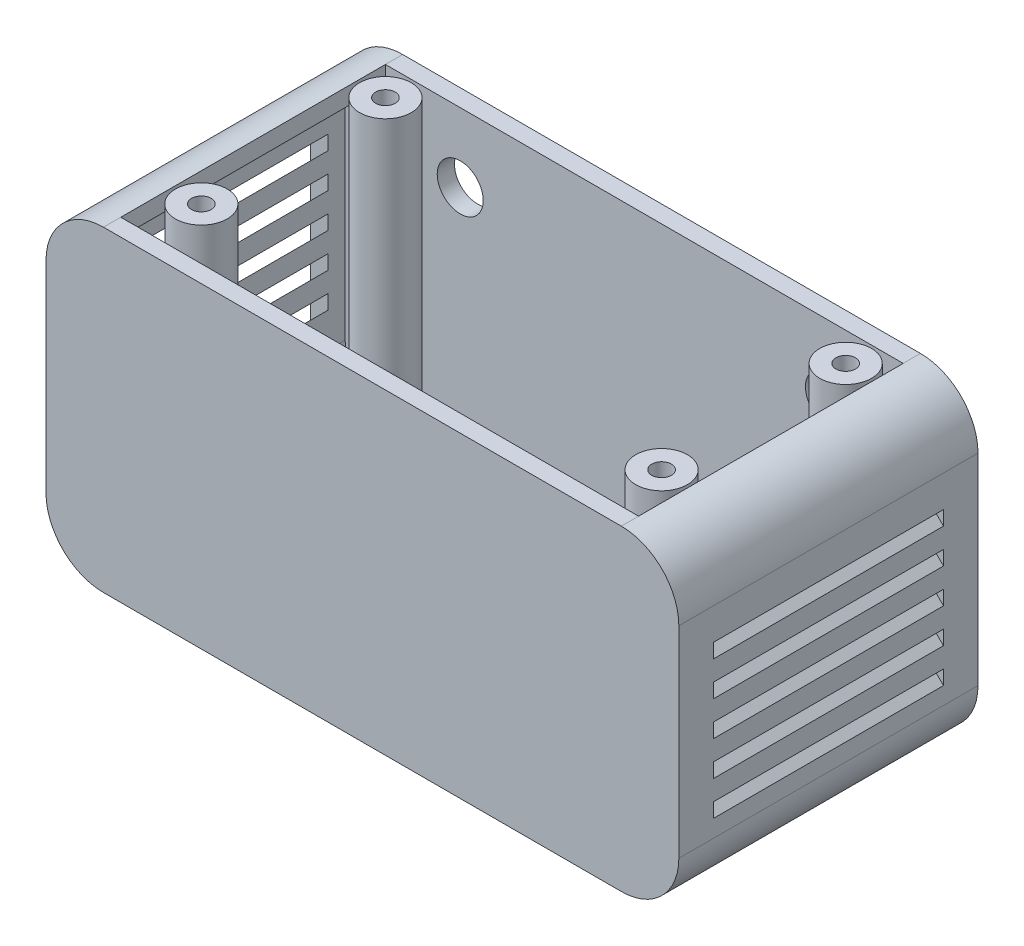
SolidWorks part; units mm, degrees
material "ABS"
ref_plane "Front Plane" through (0, 0, 0) normal (0, 0, 1) x (1, 0, 0)
ref_plane "Top Plane" through (0, 0, 0) normal (0, 1, 0) x (1, 0, 0)
ref_plane "Right Plane" through (0, 0, 0) normal (1, 0, 0) x (0, 0, -1)
sketch "Sketch1" plane through (0, 0, 0) normal (0, 0, 1) x (1, 0, 0)
  line L0 (-45, -55) -> (45, -55)
  line L1 (55, -45) -> (55, -10)
  line L2 (45, 0) -> (-45, 0)
  line L3 (-55, -10) -> (-55, -45)
  arc A0 (45, -55) -> (55, -45) centre (45, -45) ccw
  arc A1 (55, -10) -> (45, 0) centre (45, -10) ccw
  arc A2 (-45, 0) -> (-55, -10) centre (-45, -10) ccw
  arc A3 (-55, -45) -> (-45, -55) centre (-45, -45) ccw
extrude "Boss-Extrude1" add sketch "Sketch1" along normal blind 52
shell "Shell1" thickness 3 removed face at (0, 0, 26)
sketch "Sketch2" plane through (0, 0, 0) normal (0, 1, 0) x (1, 0, 0)
  circle A0 centre (-40, -8) radius 4.5
  circle A1 centre (40, -8) radius 4.5
  circle A2 centre (-40, -40) radius 4.5
  circle A3 centre (40, -40) radius 4.5
extrude "Boss-Extrude2" add sketch "Sketch2" against normal blind 52
sketch "Sketch3" plane through (0, -55, 0) normal (0, -1, 0) x (1, 0, 0)
  circle A0 centre (-40, 8) radius 3.25
  circle A1 centre (40, 8) radius 3.25
  circle A2 centre (-40, 40) radius 3.25
  circle A3 centre (40, 40) radius 3.25
extrude "Cut-Extrude1" cut sketch "Sketch3" against normal blind 49
sketch "Sketch4" plane through (0, -6, 0) normal (0, -1, 0) x (1, 0, 0)
  circle A0 centre (-40, 8) radius 1.7
  circle A1 centre (40, 8) radius 1.7
  circle A2 centre (-40, 40) radius 1.7
  circle A3 centre (40, 40) radius 1.7
extrude "Cut-Extrude2" cut sketch "Sketch4" against normal through all
ref_plane "Plane1" through (0, 0, 26) normal (0, 0, 1) x (1, 0, 0)
sketch "Sketch5" plane through (0, 0, 26) normal (0, 0, 1) x (1, 0, 0)
  line L0 (-51, -14) -> (-51, -11.5)
  line L1 (-51, -11.5) -> (-55.5, -16)
  line L2 (-55.5, -16) -> (-55.5, -18.5)
  line L3 (-55.5, -18.5) -> (-51, -14)
  line L4 (51, -14) -> (51, -11.5)
  line L5 (51, -11.5) -> (55.5, -16)
  line L6 (55.5, -16) -> (55.5, -18.5)
  line L7 (55.5, -18.5) -> (51, -14)
  line L8 (-51, -20) -> (-51, -17.5)
  line L9 (-51, -17.5) -> (-55.5, -22)
  line L10 (-55.5, -22) -> (-55.5, -24.5)
  line L11 (-55.5, -24.5) -> (-51, -20)
  line L12 (51, -20) -> (51, -17.5)
  line L13 (51, -17.5) -> (55.5, -22)
  line L14 (55.5, -22) -> (55.5, -24.5)
  line L15 (55.5, -24.5) -> (51, -20)
  line L16 (-51, -26) -> (-51, -23.5)
  line L17 (-51, -23.5) -> (-55.5, -28)
  line L18 (-55.5, -28) -> (-55.5, -30.5)
  line L19 (-55.5, -30.5) -> (-51, -26)
  line L20 (51, -26) -> (51, -23.5)
  line L21 (51, -23.5) -> (55.5, -28)
  line L22 (55.5, -28) -> (55.5, -30.5)
  line L23 (55.5, -30.5) -> (51, -26)
  line L24 (-51, -32) -> (-51, -29.5)
  line L25 (-51, -29.5) -> (-55.5, -34)
  line L26 (-55.5, -34) -> (-55.5, -36.5)
  line L27 (-55.5, -36.5) -> (-51, -32)
  line L28 (51, -32) -> (51, -29.5)
  line L29 (51, -29.5) -> (55.5, -34)
  line L30 (55.5, -34) -> (55.5, -36.5)
  line L31 (55.5, -36.5) -> (51, -32)
  line L32 (-51, -38) -> (-51, -35.5)
  line L33 (-51, -35.5) -> (-55.5, -40)
  line L34 (-55.5, -40) -> (-55.5, -42.5)
  line L35 (-55.5, -42.5) -> (-51, -38)
  line L36 (51, -38) -> (51, -35.5)
  line L37 (51, -35.5) -> (55.5, -40)
  line L38 (55.5, -40) -> (55.5, -42.5)
  line L39 (55.5, -42.5) -> (51, -38)
extrude "Cut-Extrude3" cut sketch "Sketch5" against normal blind 20 and the other way blind 20
sketch "Sketch6" plane through (0, -55, 0) normal (0, -1, 0) x (1, 0, 0)
  line L0 (-33, 12) -> (-33, 40) construction
  line L1 (-34.5, 12) -> (-34.5, 40)
  line L2 (-31.5, 12) -> (-31.5, 40)
  line L3 (-27, 12) -> (-27, 40) construction
  line L4 (-28.5, 12) -> (-28.5, 40)
  line L5 (-25.5, 12) -> (-25.5, 40)
  line L6 (-21, 12) -> (-21, 40) construction
  line L7 (-22.5, 12) -> (-22.5, 40)
  line L8 (-19.5, 12) -> (-19.5, 40)
  line L9 (-15, 12) -> (-15, 40) construction
  line L10 (-16.5, 12) -> (-16.5, 40)
  line L11 (-13.5, 12) -> (-13.5, 40)
  line L12 (-9, 12) -> (-9, 40) construction
  line L13 (-10.5, 12) -> (-10.5, 40)
  line L14 (-7.5, 12) -> (-7.5, 40)
  line L15 (-3, 12) -> (-3, 40) construction
  line L16 (-4.5, 12) -> (-4.5, 40)
  line L17 (-1.5, 12) -> (-1.5, 40)
  line L18 (3, 12) -> (3, 40) construction
  line L19 (1.5, 12) -> (1.5, 40)
  line L20 (4.5, 12) -> (4.5, 40)
  line L21 (9, 12) -> (9, 40) construction
  line L22 (7.5, 12) -> (7.5, 40)
  line L23 (10.5, 12) -> (10.5, 40)
  line L24 (15, 12) -> (15, 40) construction
  line L25 (13.5, 12) -> (13.5, 40)
  line L26 (16.5, 12) -> (16.5, 40)
  line L27 (21, 12) -> (21, 40) construction
  line L28 (19.5, 12) -> (19.5, 40)
  line L29 (22.5, 12) -> (22.5, 40)
  arc A0 (-34.5, 12) -> (-31.5, 12) centre (-33, 12) ccw
  arc A1 (-31.5, 40) -> (-34.5, 40) centre (-33, 40) ccw
  arc A2 (-28.5, 12) -> (-25.5, 12) centre (-27, 12) ccw
  arc A3 (-25.5, 40) -> (-28.5, 40) centre (-27, 40) ccw
  arc A4 (-22.5, 12) -> (-19.5, 12) centre (-21, 12) ccw
  arc A5 (-19.5, 40) -> (-22.5, 40) centre (-21, 40) ccw
  arc A6 (-16.5, 12) -> (-13.5, 12) centre (-15, 12) ccw
  arc A7 (-13.5, 40) -> (-16.5, 40) centre (-15, 40) ccw
  arc A8 (-10.5, 12) -> (-7.5, 12) centre (-9, 12) ccw
  arc A9 (-7.5, 40) -> (-10.5, 40) centre (-9, 40) ccw
  arc A10 (-4.5, 12) -> (-1.5, 12) centre (-3, 12) ccw
  arc A11 (-1.5, 40) -> (-4.5, 40) centre (-3, 40) ccw
  arc A12 (1.5, 12) -> (4.5, 12) centre (3, 12) ccw
  arc A13 (4.5, 40) -> (1.5, 40) centre (3, 40) ccw
  arc A14 (7.5, 12) -> (10.5, 12) centre (9, 12) ccw
  arc A15 (10.5, 40) -> (7.5, 40) centre (9, 40) ccw
  arc A16 (13.5, 12) -> (16.5, 12) centre (15, 12) ccw
  arc A17 (16.5, 40) -> (13.5, 40) centre (15, 40) ccw
  arc A18 (19.5, 12) -> (22.5, 12) centre (21, 12) ccw
  arc A19 (22.5, 40) -> (19.5, 40) centre (21, 40) ccw
  point P2 (-33, 26)
  point P7 (-27, 26)
  point P14 (-21, 26)
  point P21 (-15, 26)
  point P28 (-9, 26)
  point P35 (-3, 26)
  point P42 (3, 26)
  point P49 (9, 26)
  point P56 (15, 26)
  point P63 (21, 26)
extrude "Cut-Extrude4" cut sketch "Sketch6" against normal blind 3.5
sketch "Sketch7" plane through (0, 0, 0) normal (0, 0, -1) x (-1, 0, 0)
  circle A0 centre (32, -12) radius 4
  circle A1 centre (-32, -12) radius 4
extrude "Cut-Extrude5" cut sketch "Sketch7" against normal blind 3.5
sketch "Sketch8" plane through (0, -52, 0) normal (0, 1, 0) x (1, 0, 0)
  line L1 (27, -43.5) -> (33, -43.5)
  line L2 (27, -43.5) -> (27, -6.5)
  line L3 (27, -6.5) -> (33, -6.5)
  line L4 (33, -43.5) -> (33, -6.5)
  line L5 (27, -43.5) -> (33, -6.5) construction
  line L6 (27, -6.5) -> (33, -43.5) construction
  point P0 (30, -25)
extrude "Boss-Extrude3" add sketch "Sketch8" along normal blind 8
sketch "Sketch9" plane through (0, -44, 0) normal (0, 1, 0) x (1, 0, 0)
  line L1 (29.05, -41.8) -> (30.95, -41.8)
  line L2 (29.05, -41.8) -> (29.05, -8.2)
  line L3 (29.05, -8.2) -> (30.95, -8.2)
  line L4 (30.95, -41.8) -> (30.95, -8.2)
  line L5 (29.05, -41.8) -> (30.95, -8.2) construction
  line L6 (29.05, -8.2) -> (30.95, -41.8) construction
  point P0 (30, -25)
extrude "Cut-Extrude6" cut sketch "Sketch9" against normal blind 6
sketch "Sketch10" plane through (0, -44, 0) normal (0, 1, 0) x (1, 0, 0)
  line L1 (30.9, -44.5) -> (33.1, -44.5)
  line L2 (30.9, -44.5) -> (30.9, -5.5)
  line L3 (30.9, -5.5) -> (33.1, -5.5)
  line L4 (33.1, -44.5) -> (33.1, -5.5)
  line L5 (30.9, -44.5) -> (33.1, -5.5) construction
  line L6 (30.9, -5.5) -> (33.1, -44.5) construction
  point P0 (32, -25)
extrude "Cut-Extrude7" cut sketch "Sketch10" against normal blind 5
sketch "Sketch11" plane through (0, -52, 0) normal (0, 1, 0) x (1, 0, 0)
  circle A0 centre (-29, -13) radius 3
  circle A1 centre (-29, -39) radius 3
  circle A2 centre (13, -13) radius 3
  circle A3 centre (13, -39) radius 3
extrude "Boss-Extrude4" add sketch "Sketch11" along normal blind 8
